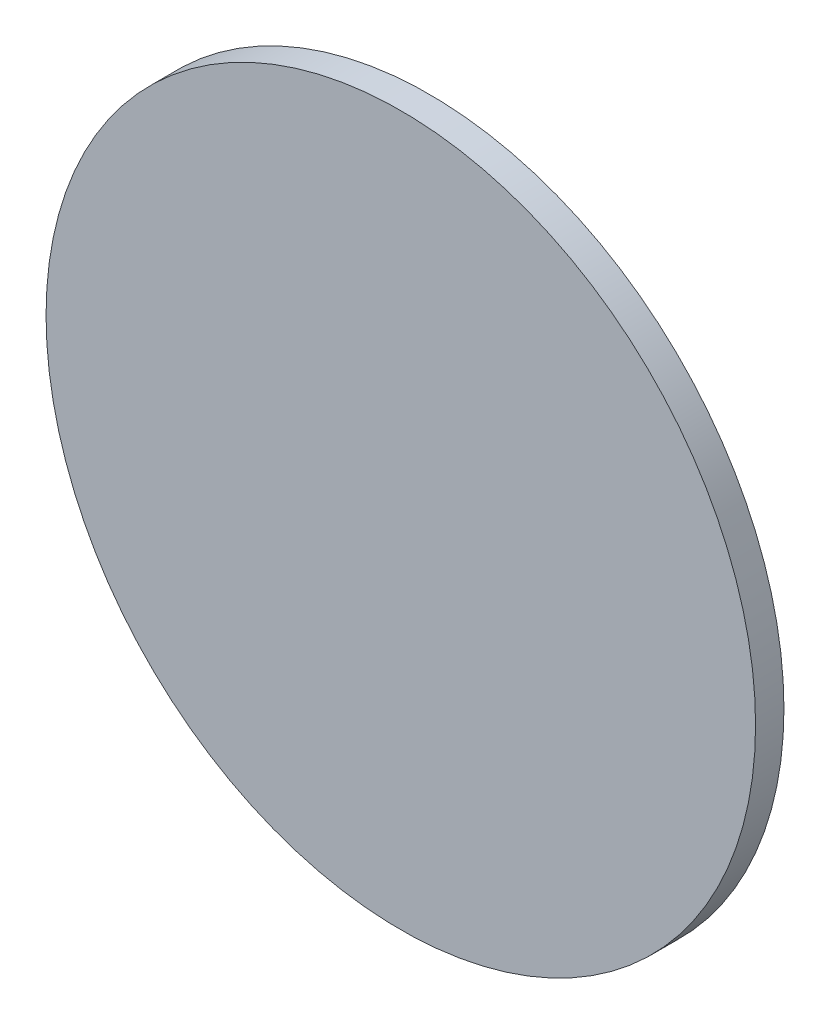
SolidWorks part; units mm, degrees
ref_plane "Front Plane" through (0, 0, 0) normal (0, 0, 1) x (1, 0, 0)
ref_plane "Top Plane" through (0, 0, 0) normal (0, 1, 0) x (1, 0, 0)
ref_plane "Right Plane" through (0, 0, 0) normal (1, 0, 0) x (0, 0, -1)
sketch "Sketch2" plane through (0, 0, 0) normal (0, 1, 0) x (1, 0, 0)
  line L0 (0, 0) -> (0, 5)
  line L1 (0, 5) -> (39.45, 5)
  line L2 (39.45, 5) -> (39.45, 2)
  line L3 (39.45, 2) -> (44.95, 2)
  line L4 (44.95, 2) -> (44.95, 5)
  line L5 (44.95, 5) -> (50.5, 5)
  line L6 (50.5, 5) -> (50.5, 2)
  line L7 (50.5, 2) -> (57.5, 2)
  line L8 (57.5, 2) -> (57.5, 5)
  line L9 (57.5, 5) -> (62.5, 5)
  line L10 (62.5, 5) -> (62.5, 0)
  line L11 (62.5, 0) -> (0, 0)
  line L12 (0, 0) -> (0, -2.4799) construction
  dimension "D1" = 5
  dimension "D2" = 78.9
  dimension "D3" = 89.9
  dimension "D4" = 101
  dimension "D5" = 115
  dimension "D6" = 5
  dimension "D7" = 3
revolve "Revolve1" add sketch "Sketch2" angle 360 about L12
